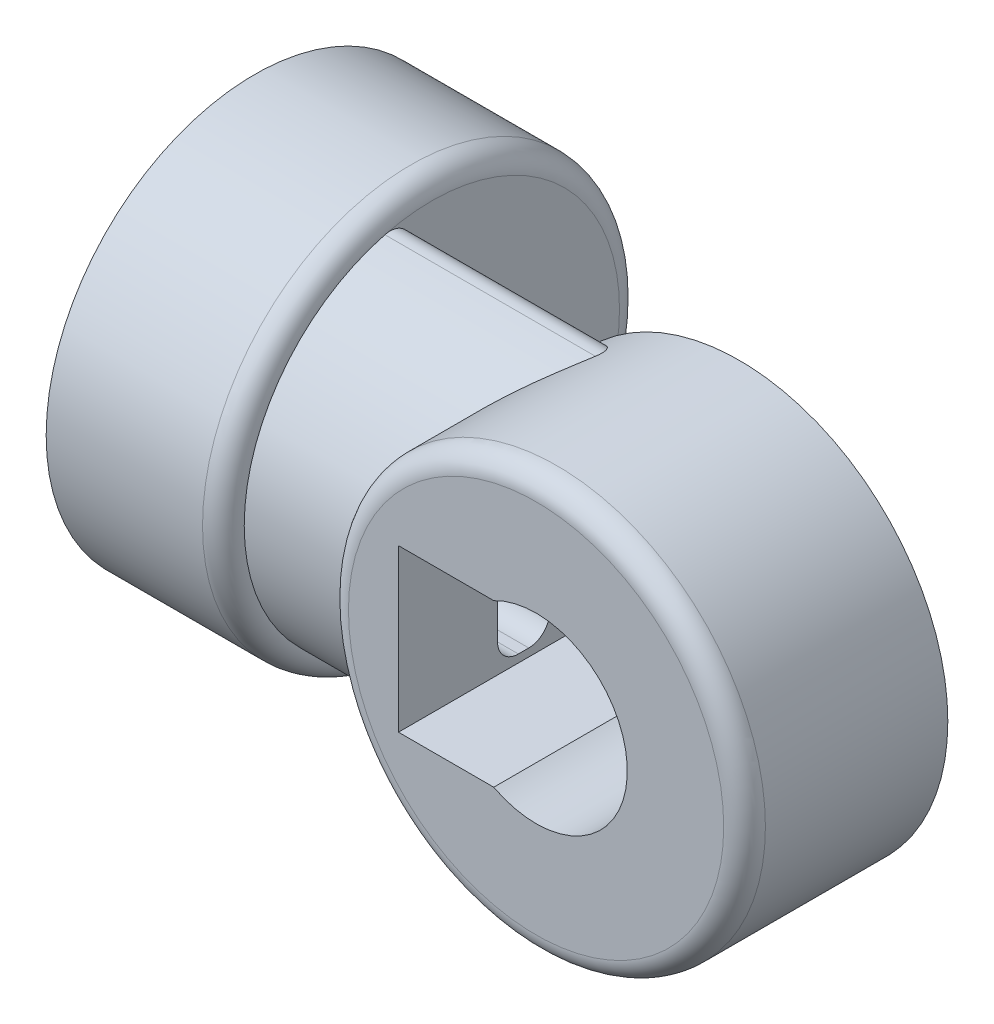
SolidWorks part; units mm, degrees
ref_plane "Front Plane" through (0, 0, 0) normal (0, 0, 1) x (1, 0, 0)
ref_plane "Top Plane" through (0, 0, 0) normal (0, 1, 0) x (1, 0, 0)
ref_plane "Right Plane" through (0, 0, 0) normal (1, 0, 0) x (0, 0, -1)
sketch "Sketch1" plane through (0, 0, 0) normal (1, 0, 0) x (0, 0, -1)
  circle A0 centre (0, 0) radius 20
  dimension "D1" = 40
extrude "Boss-Extrude1" add sketch "Sketch1" along normal blind 17
sketch "Sketch2" plane through (0, 0, 0) normal (1, 0, 0) x (0, 0, -1)
  circle A0 centre (0, 0) radius 3
  dimension "D1" = 6
extrude "Cut-Extrude2" cut sketch "Sketch2" along normal blind 11
sketch "Sketch3" plane through (0, 0, 0) normal (1, 0, 0) x (0, 0, -1)
  line L1 (0, 0) -> (-8, 0) construction
  circle A2 centre (0, 0) radius 5.9
  circle A3 centre (0, 0) radius 9 construction
  dimension "D1" = 11.8
  dimension "D2" = 18
extrude "Cut-Extrude4" cut sketch "Sketch3" along normal blind 3
ref_plane "Plane1" through (0, 0, -20) normal (0, 0, -1) x (-1, 0, 0)
sketch "Sketch4" plane through (0, 0, -20) normal (0, 0, -1) x (-1, 0, 0)
  line L0 (0, -20) -> (0, 20) construction
  line L1 (0, 0) -> (-20.0263, 0) construction
  circle A0 centre (-7.5, 0) radius 1.5
  dimension "D1" = 3
  dimension "D2" = 7.5
extrude "Cut-Extrude5" cut sketch "Sketch4" against normal blind 20
sketch "Sketch5" plane through (0, 0, -20) normal (0, 0, -1) x (-1, 0, 0)
  line L0 (0, 0) -> (-18.9115, 0) construction
  line L5 (-7.5, 0) -> (-7.5, -6.5526) construction
  circle A0 centre (-7.5, 0) radius 2.35
  dimension "D1" = 4.7
extrude "Cut-Extrude6" cut sketch "Sketch5" against normal blind 5
thread "Thread1" pitch 0.5 method cut profile "Thread Profile1" start angle 0, offset 0, length 13, pitch 0.5, diameter 3
ref_plane "Plane2" through (9, 0, -15) normal (0, -1, 0) x (1, 0, 0)
sketch "Thread Profile1" plane through (9, 0, -15) normal (0, -1, 0) x (1, 0, 0)
  line L0 (0, 0) -> (0, 0.5) construction
  line L1 (0, 0) -> (0.2706, 0.1562)
  line L2 (0.2706, 0.1562) -> (0.2706, 0.2187)
  line L3 (0.2706, 0.2187) -> (0, 0.375)
  line L4 (0.2706, 0.1875) -> (0, 0.1875) construction
  line L11 (0, 0) -> (0, 0.375)
  point P2 (0, 0)
  dimension "Pitch" = 0.5
  dimension "Profile_Angle" = 60
  dimension "Profile_Land" = 0.0625
  dimension "Profile_Height" = 0.2706
fillet "Fillet2" radius 2 1 edges at (17, 0, -20)
ref_plane "Plane3" through (17, 0, 0) normal (1, 0, 0) x (0, 0, -1)
sketch "Sketch8" plane through (17, 0, 0) normal (1, 0, 0) x (0, 0, -1)
  line L0 (0, 18) -> (0, -18) construction
  line L1 (-2, 17.8885) -> (-2, -17.8885)
  line L2 (0, 0) -> (-31.6499, 0) construction
  circle A0 centre (0, 0) radius 18 construction
  arc A1 (-2, 17.8885) -> (-2, -17.8885) centre (0, 0) ccw
  point P8 (0, 0)
  dimension "D1" = 2
extrude "Boss-Extrude3" add sketch "Sketch8" along normal blind 30
ref_plane "Plane4" through (0, 0, 2) normal (0, 0, -1) x (-1, 0, 0)
sketch "Sketch9" plane through (0, 0, 2) normal (0, 0, -1) x (-1, 0, 0)
  line L0 (0, 0) -> (-48.0689, 0) construction
  line L1 (-47, -17.8885) -> (-47, 17.8885) construction
  circle A0 centre (-47, 0) radius 20
  dimension "D1" = 40
extrude "Boss-Extrude4" add sketch "Sketch9" against normal blind 18 and the other way blind 1.5
fillet "Fillet3" radius 2 1 edges at (27, 0, 20)
ref_plane "Plane5" through (0, 0, 20) normal (0, 0, 1) x (1, 0, 0)
sketch "Sketch10" plane through (0, 0, 20) normal (0, 0, 1) x (1, 0, 0)
  line L0 (0, 0) -> (59.3842, 0) construction
  line L3 (47, 20) -> (47, -20) construction
  line L4 (42.938, 7.75) -> (33.8, 7.75)
  line L6 (42.938, -7.75) -> (33.8, -7.75)
  line L7 (33.8, 7.75) -> (33.8, -7.75)
  arc A1 (42.938, -7.75) -> (42.938, 7.75) centre (47, 0) ccw
  circle A2 centre (47, 0) radius 20 construction
  dimension "D2" = 17.5
  dimension "D3" = 13.2
  dimension "D4" = 7.75
  dimension "D5" = 15.5
extrude "Cut-Extrude8" cut sketch "Sketch10" against normal blind 18 contours A1 L4 L7 L6
sketch "Sketch12" plane through (0, 0, 0) normal (0, 0, 1) x (1, 0, 0)
  line L0 (0, 0) -> (47, 0) construction
  line L2 (47, 20) -> (47, -20) construction
  circle A0 centre (47, 0) radius 3.75
  circle A3 centre (47, 0) radius 20 construction
  point P15 (47, 0)
  dimension "D1" = 7.5
extrude "Cut-Extrude9" cut sketch "Sketch12" along normal blind 19
ref_plane "Plane6" through (33.8, 0, 0) normal (1, 0, 0) x (0, 0, -1)
sketch "Sketch13" plane through (33.8, 0, 0) normal (1, 0, 0) x (0, 0, -1)
  line L0 (0, 0) -> (-26.2167, 0) construction
  line L1 (-10.5, 7) -> (-5.5, 7)
  line L2 (-10.5, 7) -> (-10.5, -7)
  line L3 (-10.5, -7) -> (-5.5, -7)
  line L4 (-5.5, 7) -> (-5.5, -7)
  line L5 (-2, -17.8885) -> (-2, 17.8885) construction
  dimension "D1" = 3.5
  dimension "D2" = 5
  dimension "D3" = 14
  dimension "D4" = 7
extrude "Cut-Extrude10" cut sketch "Sketch13" against normal blind 28
ref_plane "Plane7" through (0, 0, 0.5) normal (0, 0, -1) x (-1, 0, 0)
sketch "Sketch14" plane through (0, 0, 0.5) normal (0, 0, -1) x (-1, 0, 0)
  line L0 (-47, 0) -> (0, 0) construction
  line L1 (-47, 0) -> (-47, -27.3781) construction
  line L3 (-48.6, -7) -> (-45.4, -7)
  line L4 (-48.6, -7) -> (-48.6, -8.7)
  line L5 (-48.6, -8.7) -> (-45.4, -8.7)
  line L6 (-45.4, -7) -> (-45.4, -8.7)
  point P9 (-45.4, -7.85)
  dimension "D1" = 7
  dimension "D2" = 3.2
  dimension "D3" = 1.6
  dimension "D4" = 1.7
extrude "Cut-Extrude11" cut sketch "Sketch14" against normal blind 1.5
fillet "Fillet5" radius 2 2 edges at (27.5279, 17.8885, 2) (27.5279, -17.8885, 2)
ref_plane "Plane11" through (0, 0, 10.5) normal (0, 0, -1) x (-1, 0, 0)
sketch "Sketch17" plane through (0, 0, 10.5) normal (0, 0, -1) x (-1, 0, 0)
  line L0 (-5.8, -7) -> (-33.8, -7) construction
  line L1 (-5.8, 7) -> (-10.8, 7)
  line L2 (-5.8, 7) -> (-5.8, -7)
  line L3 (-5.8, -7) -> (-10.8, -7)
  line L4 (-10.8, 7) -> (-10.8, -7)
  dimension "D1" = 5
extrude "Cut-Extrude12" cut sketch "Sketch17" against normal blind 5
ref_plane "Plane12" through (5.8, 0, 0) normal (1, 0, 0) x (0, 0, -1)
sketch "Sketch18" plane through (5.8, 0, 0) normal (1, 0, 0) x (0, 0, -1)
  line L0 (-5.5, 7) -> (-15.5, 7) construction
  line L1 (-15.5, -7) -> (-10.5, -7)
  line L2 (-15.5, -7) -> (-15.5, 7)
  line L3 (-15.5, 7) -> (-10.5, 7)
  line L4 (-10.5, -7) -> (-10.5, 7)
  dimension "D1" = 5
extrude "Cut-Extrude13" cut sketch "Sketch18" against normal blind 7
fillet "Fillet6" radius 2 16 edges at (5.8, -7, 8) (5.8, 7, 8) (10.8, 7, 13) (10.8, -7, 13) (2.9, -7, 10.5) (5.4, -7, 15.5) (2.9, 7, 10.5) (5.4, 7, 15.5) (5.8, 0, 10.5) (10.8, 0, 15.5) (10.8, 0, 10.5) (5.8, 0, 5.5) (22.3, -7, 10.5) (22.3, 7, 10.5) (19.8, -7, 5.5) (19.8, 7, 5.5)
sketch "Sketch19" plane through (0, 0, 0.5) normal (0, 0, -1) x (-1, 0, 0)
  line L0 (-33.8, 7.75) -> (-33.8, -7.75) construction
  circle A0 centre (-30.4, 0) radius 2.5
  point P2 (-30.3857, 0)
  dimension "D1" = 5
  dimension "D2" = 3.4
extrude "Cut-Extrude14" cut sketch "Sketch19" against normal blind 5
